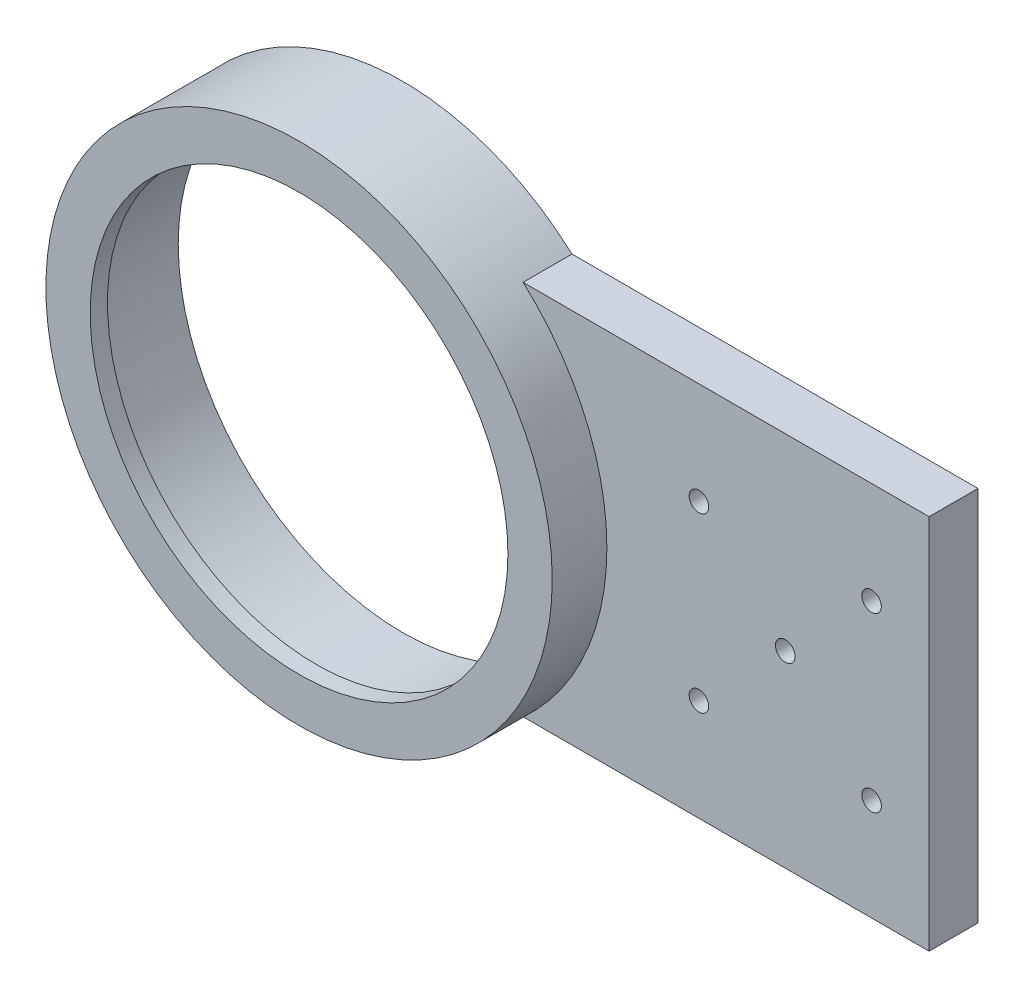
SolidWorks part; units mm, degrees
material "7075-O (SS)"
ref_plane "Front" through (0, 0, 0) normal (0, 0, 1) x (1, 0, 0)
ref_plane "Top" through (0, 0, 0) normal (0, 1, 0) x (1, 0, 0)
ref_plane "Right" through (0, 0, 0) normal (1, 0, 0) x (0, 0, -1)
sketch "Croquis1" plane through (0, 0, 0) normal (0, 0, 1) x (1, 0, 0)
  circle A0 centre (0, 0) radius 36.3
  circle A1 centre (0, 0) radius 44
  dimension "D1" = 72.6
  dimension "D2" = 88
extrude "Saliente-Extruir1" add sketch "Croquis1" along normal blind 3
sketch "Croquis2" plane through (0, 0, 0) normal (0, 0, -1) x (-1, 0, 0)
  circle A0 centre (0, 0) radius 39
  circle A1 centre (0, 0) radius 44 construction
  circle A2 centre (0, 0) radius 44
  dimension "D1" = 78
extrude "Saliente-Extruir2" add sketch "Croquis2" along normal blind 15
sketch "Croquis3" plane through (0, 0, -15) normal (0, 0, -1) x (-1, 0, 0)
  line L0 (-29.4399, 32.7) -> (-100, 32.7)
  line L1 (-100, 32.7) -> (-100, -32.7)
  line L2 (-100, -32.7) -> (-29.4399, -32.7)
  line L3 (10.5108, 0) -> (-10.5108, 0) construction
  line L4 (0, 10.5108) -> (0, -10.5108) construction
  circle A0 centre (0, 0) radius 44 construction
  arc A1 (-29.4399, 32.7) -> (-29.4399, -32.7) centre (0, 0) ccw
  point P9 (-100, 0)
  dimension "D1" = 65.4
  dimension "D2" = 100
extrude "Saliente-Extruir3" add sketch "Croquis3" against normal blind 8.5
hole_wizard "Taladro de margen para M31" positions "Croquis4" profile "Croquis5" hole size "M3" standard "Ansi Metric" end condition up to next
sketch "Croquis4" plane through (0, 0, -15) normal (0, 0, -1) x (-1, 0, 0)
  line L1 (-60, -15) -> (-90, -15) construction
  line L2 (-60, -15) -> (-60, 15) construction
  line L3 (-60, 15) -> (-90, 15) construction
  line L4 (-90, -15) -> (-90, 15) construction
  line L5 (-60, -15) -> (-90, 15) construction
  line L6 (-60, 15) -> (-90, -15) construction
  line L7 (9.9, 0) -> (-9.9, 0) construction
  line L8 (-100, 32.7) -> (-100, -32.7) construction
  point P1 (-75, 0)
  point P2 (-90, 15)
  point P35 (-60, -15)
  point P36 (-60, 15)
  point P37 (-90, -15)
  dimension "D1" = 30
  dimension "D2" = 25
sketch "Croquis5" plane through (75, 0, -15) normal (1, 0, 0) x (0, 1, 0)
  line L0 (0, 0) -> (0, 8.5)
  line L1 (0, 8.5) -> (1.7, 8.5)
  line L2 (1.7, 8.5) -> (1.7, 0)
  line L5 (1.7, 0) -> (0, 0)
  line L11 (0, -6.35) -> (0, 107.95) construction
  dimension "Diámetro de taladro hasta el siguiente" = 3.4
  dimension "Profundidad de taladro hasta el siguiente" = 8.5
